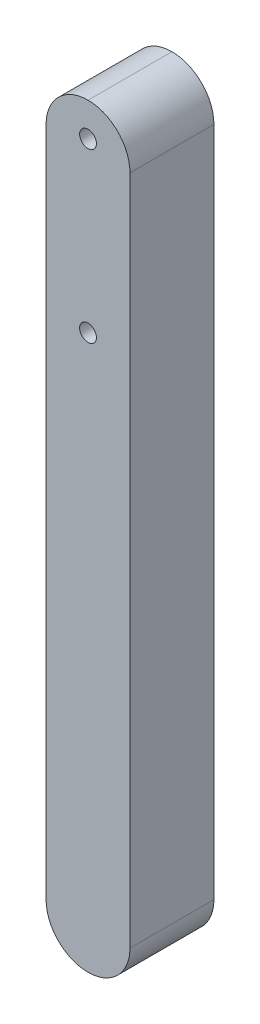
SolidWorks part; units mm, degrees
ref_plane "Front" through (0, 0, 0) normal (0, 0, 1) x (1, 0, 0)
ref_plane "Top" through (0, 0, 0) normal (0, 1, 0) x (1, 0, 0)
ref_plane "Right" through (0, 0, 0) normal (1, 0, 0) x (0, 0, -1)
sketch "Esquisse1" plane through (0, 0, 0) normal (0, 0, 1) x (1, 0, 0)
  line L1 (0, 0) -> (10, 0)
  line L2 (0, 0) -> (0, 90)
  line L3 (0, 90) -> (10, 90)
  line L4 (10, 0) -> (10, 90)
  dimension "D1" = 10
  dimension "D2" = 90
extrude "Boss.-Extru.1" add sketch "Esquisse1" along normal blind 10
sketch "Esquisse2" plane through (0, 0, 10) normal (0, 0, 1) x (1, 0, 0)
  line L0 (5, 90) -> (5, 66) construction
  line L1 (10, 90) -> (0, 90) construction
  circle A0 centre (5, 66) radius 1
  circle A1 centre (5, 86) radius 1
  point P7 (5, 74.8189)
  dimension "D1" = 20
  dimension "D2" = 4
  dimension "D3" = 2
extrude "Enlèv. mat.-Extru.1" cut sketch "Esquisse2" against normal up to vertex (10 mm away) up to point (0, 90, 0)
fillet "Congé1" radius 5 4 edges at (10, 90, 5) (0, 90, 5) (10, 0, 5) (0, 0, 5)
